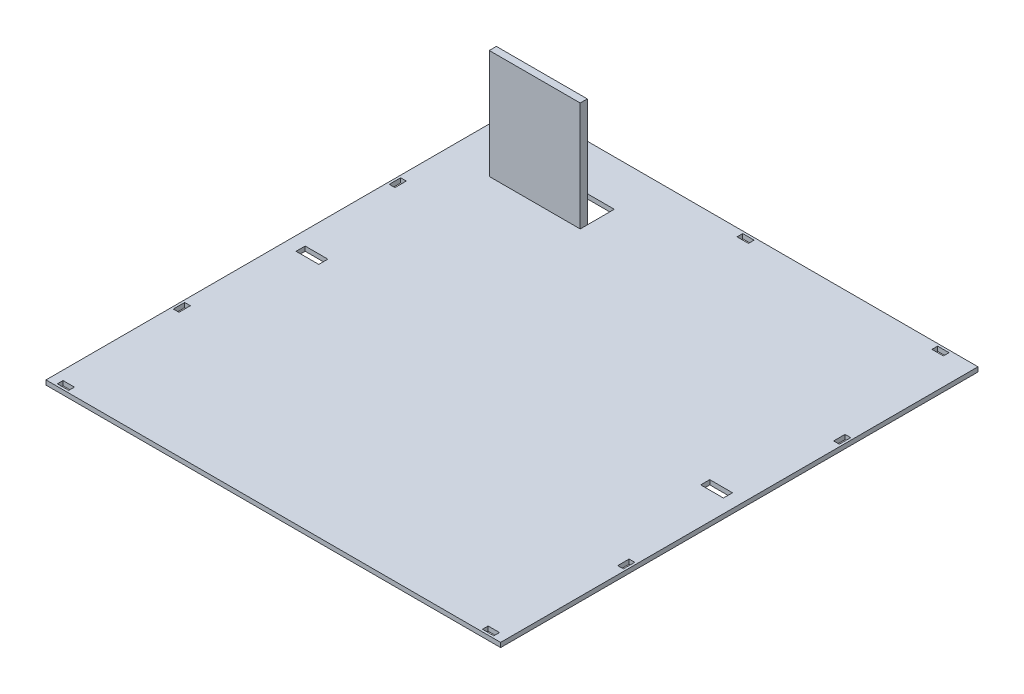
SolidWorks part; units mm, degrees
material "ABS"
ref_plane "Front Plane" through (0, 0, 0) normal (0, 0, 1) x (1, 0, 0)
ref_plane "Top Plane" through (0, 0, 0) normal (0, 1, 0) x (1, 0, 0)
ref_plane "Right Plane" through (0, 0, 0) normal (1, 0, 0) x (0, 0, -1)
sketch "Sketch1" plane through (0, 0, 0) normal (0, 1, 0) x (1, 0, 0)
  line L0 (-80, 73.1246) -> (-40, 73.1246)
  line L1 (100, 105) -> (-100, 105)
  line L2 (100, 105) -> (100, -105)
  line L3 (100, -105) -> (-100, -105)
  line L4 (-100, 105) -> (-100, -105)
  line L5 (100, 105) -> (-100, -105) construction
  line L6 (100, -105) -> (-100, 105) construction
  line L11 (94, 3) -> (84, 3)
  line L12 (94, 3) -> (94, -1)
  line L13 (94, -1) -> (84, -1)
  line L14 (84, 3) -> (84, -1)
  line L15 (94, 3) -> (84, -1) construction
  line L16 (94, -1) -> (84, 3) construction
  line L17 (-94, -1) -> (-84, -1)
  line L18 (-94, -1) -> (-94, 3)
  line L19 (-94, 3) -> (-84, 3)
  line L20 (-84, -1) -> (-84, 3)
  line L21 (-94, -1) -> (-84, 3) construction
  line L22 (-94, 3) -> (-84, -1) construction
  line L27 (-80, 70) -> (-40, 70)
  line L28 (-80, 70) -> (-80, 85)
  line L33 (-80, 85) -> (-40, 85)
  line L34 (-40, 70) -> (-40, 85)
  line L35 (96, -104) -> (91, -104)
  line L36 (96, -104) -> (96, -101.5)
  line L37 (96, -101.5) -> (91, -101.5)
  line L38 (91, -104) -> (91, -101.5)
  line L39 (96, -104) -> (91, -101.5) construction
  line L40 (96, -101.5) -> (91, -104) construction
  line L41 (-2.5, 101.5) -> (2.5, 101.5)
  line L42 (-2.5, 101.5) -> (-2.5, 104)
  line L43 (-2.5, 104) -> (2.5, 104)
  line L44 (2.5, 101.5) -> (2.5, 104)
  line L45 (-2.5, 101.5) -> (2.5, 104) construction
  line L46 (-2.5, 104) -> (2.5, 101.5) construction
  line L47 (-96, -104) -> (-91, -104)
  line L48 (-96, -104) -> (-96, -101.5)
  line L49 (-96, -101.5) -> (-91, -101.5)
  line L50 (-91, -104) -> (-91, -101.5)
  line L51 (-96, -104) -> (-91, -101.5) construction
  line L52 (-96, -101.5) -> (-91, -104) construction
  line L53 (-80.75, 104) -> (-85.75, 104)
  line L54 (-80.75, 104) -> (-80.75, 101.5)
  line L55 (-80.75, 101.5) -> (-85.75, 101.5)
  line L56 (-85.75, 104) -> (-85.75, 101.5)
  line L57 (-80.75, 104) -> (-85.75, 101.5) construction
  line L58 (-80.75, 101.5) -> (-85.75, 104) construction
  line L59 (83.25, 101.5) -> (88.25, 101.5)
  line L60 (83.25, 101.5) -> (83.25, 104)
  line L61 (83.25, 104) -> (88.25, 104)
  line L62 (88.25, 101.5) -> (88.25, 104)
  line L63 (83.25, 101.5) -> (88.25, 104) construction
  line L64 (83.25, 104) -> (88.25, 101.5) construction
  line L65 (99, -45) -> (96.5, -45)
  line L66 (99, -45) -> (99, -50)
  line L67 (99, -50) -> (96.5, -50)
  line L68 (96.5, -45) -> (96.5, -50)
  line L69 (99, -45) -> (96.5, -50) construction
  line L70 (99, -50) -> (96.5, -45) construction
  line L71 (99, 50) -> (96.5, 50)
  line L72 (99, 50) -> (99, 45)
  line L73 (99, 45) -> (96.5, 45)
  line L74 (96.5, 50) -> (96.5, 45)
  line L75 (99, 50) -> (96.5, 45) construction
  line L76 (99, 45) -> (96.5, 50) construction
  line L77 (-99, -45) -> (-96.5, -45)
  line L78 (-99, -45) -> (-99, -50)
  line L79 (-99, -50) -> (-96.5, -50)
  line L80 (-96.5, -45) -> (-96.5, -50)
  line L81 (-99, -45) -> (-96.5, -50) construction
  line L82 (-99, -50) -> (-96.5, -45) construction
  line L83 (-99, 45) -> (-96.5, 45)
  line L84 (-99, 45) -> (-99, 50)
  line L85 (-99, 50) -> (-96.5, 50)
  line L86 (-96.5, 45) -> (-96.5, 50)
  line L87 (-99, 45) -> (-96.5, 50) construction
  line L88 (-99, 50) -> (-96.5, 45) construction
  line L89 (-80, 70) -> (-40, 85) construction
  line L90 (-80, 85) -> (-40, 70) construction
  point P0 (0, 0)
  point P6 (89, 1)
  point P11 (-60, 77.5)
  point P23 (-89, 1)
  point P38 (93.5, -102.75)
  point P43 (0, 102.75)
  point P48 (-93.5, -102.75)
  point P53 (-83.25, 102.75)
  point P58 (85.75, 102.75)
  point P59 (97.75, -47.5)
  point P68 (97.75, -45)
  point P69 (97.75, 47.5)
  point P74 (-97.75, -47.5)
  point P79 (-97.75, 47.5)
  dimension "D7" = 20
  dimension "D8" = 20
  dimension "D9" = 15
  dimension "D11" = 1
  dimension "D17" = 10
  dimension "D1" = 200
  dimension "D2" = 210
  dimension "D6" = 104
  dimension "D10" = 40
  dimension "D16" = 6
  dimension "D18" = 4
  dimension "D19" = 104
  dimension "D20" = 6
  dimension "D21" = 4
  dimension "D22" = 10
  dimension "D31" = 4
  dimension "D32" = 1
  dimension "D33" = 5
  dimension "D34" = 2.5
  dimension "D36" = 100
  dimension "D37" = 5
  dimension "D38" = 2.5
  dimension "D39" = 1
  dimension "D40" = 4
  dimension "D41" = 5
  dimension "D42" = 2.5
  dimension "D43" = 14.25
  dimension "D44" = 1
  dimension "D45" = 5
  dimension "D46" = 2.5
  dimension "D47" = 14.25
  dimension "D48" = 1
  dimension "D49" = 5
  dimension "D50" = 2.5
  dimension "D51" = 1
  dimension "D52" = 5
  dimension "D53" = 2.5
  dimension "D54" = 55
  dimension "D55" = 55
  dimension "D56" = 1
  dimension "D57" = 5
  dimension "D58" = 2.5
  dimension "D59" = 1
  dimension "D60" = 55
  dimension "D61" = 2.5
  dimension "D62" = 5
  dimension "D63" = 55
  dimension "D64" = 1
  dimension "D65" = 2.5
  dimension "D66" = 5
extrude "MainBody" add sketch "Sketch1" along normal blind 2 contours L1 L4 L3 L2 L86 L83 L84 L85 L74 L71 L72 L73 L68 L65 L66 L67 L62 L59 L60 L61 L56 L53 L54 L55 L50 L47 L48 L49 L44 L41 L42 L43 L20 L17 L18 L19 L14 L11 L12 L13 L35 region at (0.8729, 0, 1.1615)
extrude "Boss-Extrude1" add sketch "Sketch1<8>" along normal blind 50 contours L27 L34 L0 L28 region at (-60, 0, -71.5623)
sketch "Sketch1<8>" plane through (0, 0, 0) normal (0, 1, 0) x (1, 0, 0) same geometry as "Sketch1"
